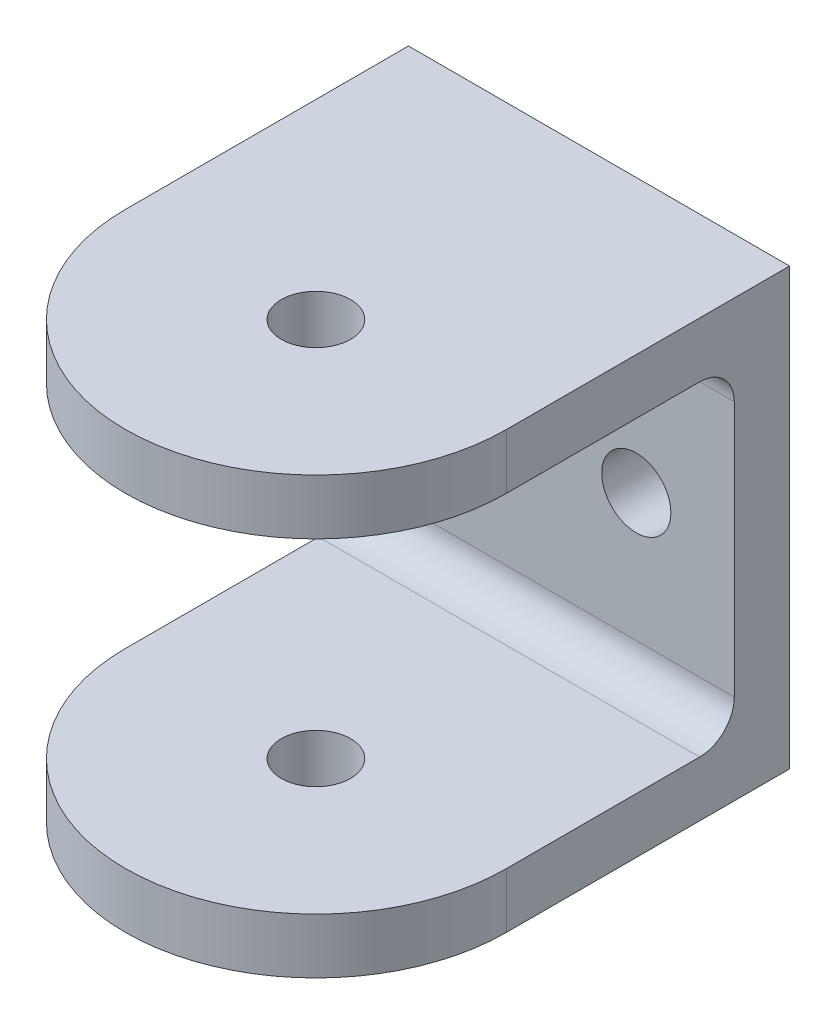
SolidWorks part; units mm, degrees
ref_plane "Front Plane" through (0, 0, 0) normal (0, 0, 1) x (1, 0, 0)
ref_plane "Top Plane" through (0, 0, 0) normal (0, 1, 0) x (1, 0, 0)
ref_plane "Right Plane" through (0, 0, 0) normal (1, 0, 0) x (0, 0, -1)
sketch "Sketch1" plane through (0, 0, 0) normal (0, 0, 1) x (1, 0, 0)
  line L0 (0, 0) -> (-8.5, 0) construction
  line L1 (-17.5, -20) -> (17.5, -20)
  line L2 (-17.5, -20) -> (-17.5, 20)
  line L3 (-17.5, 20) -> (17.5, 20)
  line L4 (17.5, -20) -> (17.5, 20)
  line L5 (-17.5, -20) -> (17.5, 20) construction
  line L6 (-17.5, 20) -> (17.5, -20) construction
  line L7 (0, 0) -> (8.5, 0) construction
  circle A0 centre (8.5, 0) radius 3.175
  circle A1 centre (-8.5, 0) radius 3.175
  point P0 (0, 0)
  point P12 (0, 0)
  point P13 (0, 0)
  dimension "D4" = 6.35
  dimension "D1" = 35
  dimension "D2" = 40
  dimension "D3" = 17
extrude "Boss-Extrude1" add sketch "Sketch1" along normal blind 5.08
sketch "Sketch2" plane through (0, 0, 5.08) normal (0, 0, 1) x (1, 0, 0)
  line L1 (-17.5, 20) -> (17.5, 20)
  line L2 (-17.5, 20) -> (-17.5, 14.92)
  line L3 (-17.5, 14.92) -> (17.5, 14.92)
  line L4 (17.5, -20) -> (17.5, 20)
  line L5 (17.5, 20) -> (-17.5, 20)
  line L6 (-17.5, 20) -> (-17.5, -20)
  line L7 (-17.5, -20) -> (17.5, -20)
  line L8 (17.5, -20) -> (17.5, 20) construction
  line L9 (17.5, 20) -> (-17.5, 20) construction
  line L10 (-17.5, 20) -> (-17.5, -20) construction
  line L11 (-17.5, -20) -> (17.5, -20) construction
  line L12 (17.5, 20) -> (17.5, 14.92)
  line L13 (17.5, -20) -> (-17.5, -20)
  line L14 (17.5, -20) -> (17.5, -14.92)
  line L15 (17.5, -14.92) -> (-17.5, -14.92)
  line L16 (-17.5, -20) -> (-17.5, -14.92)
  dimension "D2" = 5.08
  dimension "D3" = 5.08
  dimension "D1" = 0
extrude "Boss-Extrude2" add sketch "Sketch2" along normal blind 39
fillet "Fillet1" radius 3.175 2 edges at (0, 14.92, 5.08) (0, -14.92, 5.08)
sketch "Sketch3" plane through (0, 20, 0) normal (0, 1, 0) x (1, 0, 0)
  line L0 (17.5, -5.08) -> (-17.5, -5.08) construction
  line L1 (17.5, -5.08) -> (-17.5, -5.08) construction
  line L2 (17.5, -44.08) -> (17.5, 0) construction
  line L3 (17.5, -44.08) -> (17.5, -26)
  line L4 (-17.5, -44.08) -> (-17.5, 0) construction
  line L5 (17.5, -44.08) -> (-17.5, -44.08) construction
  line L6 (-17.5, -44.08) -> (-17.5, -26)
  line L7 (17.5, -44.08) -> (-17.5, -44.08)
  circle A0 centre (0, -26) radius 3.175
  arc A1 (-17.5, -26) -> (17.5, -26) centre (0, -26) ccw
  point P4 (0, -5.08)
  dimension "D1" = 6.35
  dimension "D2" = 20.92
extrude "Cut-Extrude1" cut sketch "Sketch3" against normal through all
